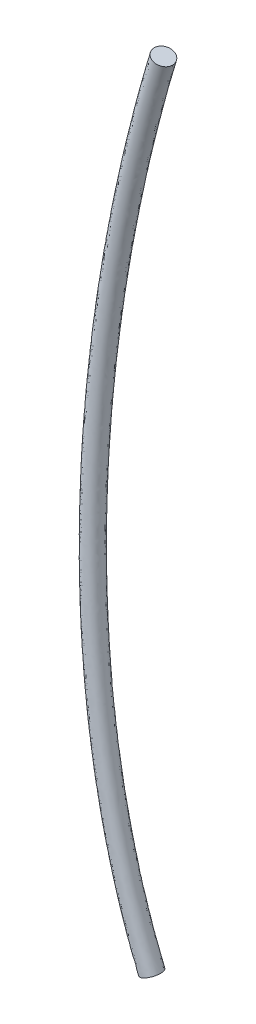
SolidWorks part; units mm, degrees
material "Custom Plastic"
ref_plane "X-Y Datum" through (0, 0, 0) normal (0, 0, 1) x (1, 0, 0)
ref_plane "X-Z Datum" through (0, 0, 0) normal (0, 1, 0) x (1, 0, 0)
ref_plane "Y-Z Datum" through (0, 0, 0) normal (1, 0, 0) x (0, 0, -1)
sketch3d "3DSketch2"
  circle A0 centre (-197.0854, 58.6266, 219.825) radius 4.5 construction
  circle A2 centre (-188.3433, -150.865, 232.459) radius 2.5146 construction
  circle A10 centre (-190.8053, 81.2719, 219.825) radius 4.5 construction
  spline S1 degree 3 poles (-190.8053, 81.2719, 219.825) (-215.8941, 1.2897, 218.3639) (-212.7716, -90.3117, 233.6078) (-181.9842, -168.3365, 232.459) knots 0 0 0 0 1 1 1 1
  point P1 (0, 0, 0)
  point P2 (-192.0065, -158.1634, 232.459)
  point P4 (0, 0, 0)
  point P6 (-191.9282, -158.1128, 232.6307)
  point P8 (-183.4325, -170.5474, 232.459)
  point P9 (-192.9603, -152.1006, 232.12)
  point P12 (-195.8828, 62.9629, 219.825)
  point P13 (-188.3433, -150.865, 232.459)
  point P16 (0, 0, 0)
  point P17 (0, 0, 0)
  point P18 (-189.2034, -148.502, 232.459)
  point P19 (0, 0, 0)
  point P20 (-181.9842, -168.3365, 232.459)
  point P24 (-192.0078, 76.9356, 219.825)
sweep "Sweep2" add path "3DSketch2" circular profile diameter 6.35 parameters "D3"=6.35
